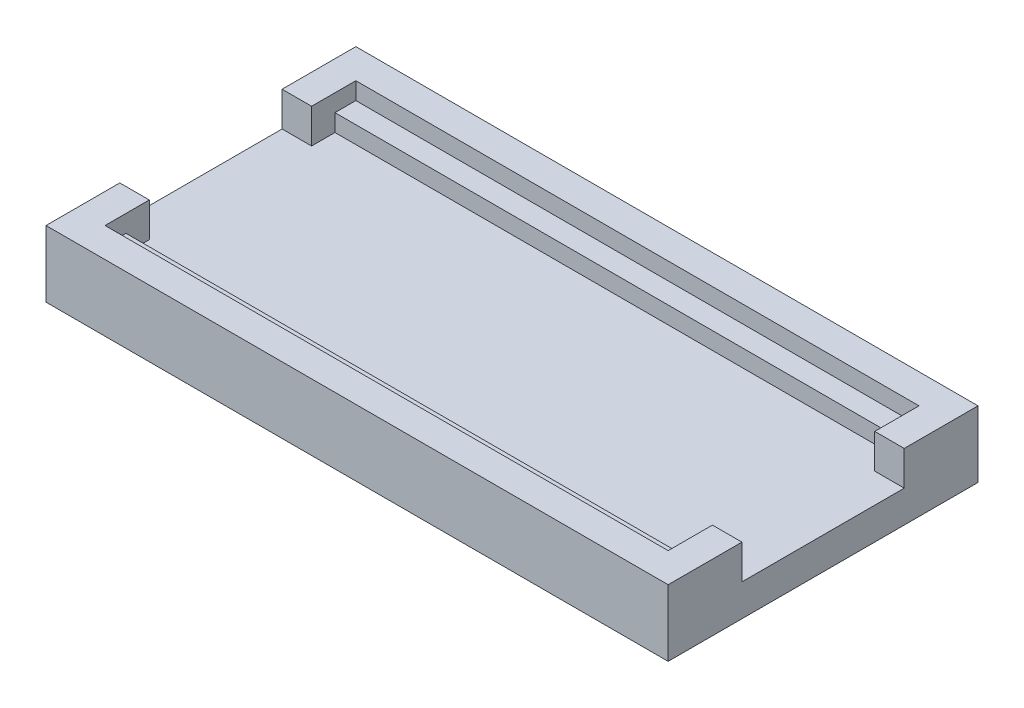
SolidWorks part; units mm, degrees
material "Delrin 2700 NC010, Low Viscosity Acetal Copolymer (SS)"
ref_plane "Front Plane" through (0, 0, 0) normal (0, 0, 1) x (1, 0, 0)
ref_plane "Top Plane" through (0, 0, 0) normal (0, 1, 0) x (1, 0, 0)
ref_plane "Right Plane" through (0, 0, 0) normal (1, 0, 0) x (0, 0, -1)
sketch "Sketch1" plane through (0, 0, 0) normal (0, 1, 0) x (1, 0, 0)
  line L1 (0, 0) -> (253, 0)
  line L2 (0, 0) -> (0, 126)
  line L3 (0, 126) -> (253, 126)
  line L4 (253, 0) -> (253, 126)
  dimension "D1" = 126
  dimension "D2" = 253
extrude "Boss-Extrude1" add sketch "Sketch1" along normal blind 27
sketch "Sketch2" plane through (0, 27, 0) normal (0, 1, 0) x (1, 0, 0)
  line L0 (0, 126) -> (0, 0) construction
  line L1 (12, 114) -> (241, 114)
  line L2 (12, 114) -> (12, 12)
  line L3 (12, 12) -> (241, 12)
  line L4 (241, 114) -> (241, 12)
  line L5 (0, 0) -> (253, 0) construction
  line L6 (253, 0) -> (253, 126) construction
  line L7 (253, 126) -> (0, 126) construction
  dimension "D1" = 12
  dimension "D2" = 12
  dimension "D3" = 12
  dimension "D4" = 12
extrude "Cut-Extrude1" cut sketch "Sketch2" against normal blind 7
sketch "Sketch3" plane through (0, 20, 0) normal (0, 1, 0) x (1, 0, 0)
  line L1 (241, 105.5) -> (12, 105.5)
  line L2 (241, 105.5) -> (241, 20.5)
  line L3 (241, 20.5) -> (12, 20.5)
  line L4 (12, 105.5) -> (12, 20.5)
  line L5 (241, 114) -> (12, 114) construction
  line L6 (12, 114) -> (12, 12) construction
  line L7 (241, 12) -> (241, 114) construction
  line L8 (12, 12) -> (241, 12) construction
  dimension "D1" = 8.5
  dimension "D3" = 8.5
extrude "Cut-Extrude2" cut sketch "Sketch3" against normal blind 7
sketch "Sketch4" plane through (0, 27, 0) normal (0, 1, 0) x (1, 0, 0)
  line L0 (0, 126) -> (0, 0) construction
  line L1 (0, 30) -> (12, 30)
  line L2 (0, 30) -> (0, 96)
  line L3 (0, 96) -> (12, 96)
  line L4 (12, 30) -> (12, 96)
  line L5 (12, 114) -> (12, 12) construction
  line L6 (0, 0) -> (253, 0) construction
  line L7 (253, 126) -> (0, 126) construction
  dimension "D1" = 30
  dimension "D2" = 30
extrude "Cut-Extrude3" cut sketch "Sketch4" against normal blind 14
sketch "Sketch5" plane through (0, 27, 0) normal (0, 1, 0) x (1, 0, 0)
  line L0 (253, 0) -> (253, 126) construction
  line L1 (253, 96) -> (241, 96)
  line L2 (253, 96) -> (253, 30)
  line L3 (253, 30) -> (241, 30)
  line L4 (241, 96) -> (241, 30)
  line L5 (241, 12) -> (241, 114) construction
  line L6 (0, 0) -> (253, 0) construction
  line L7 (253, 126) -> (0, 126) construction
  dimension "D1" = 30
  dimension "D2" = 30
extrude "Cut-Extrude4" cut sketch "Sketch5" against normal blind 14
